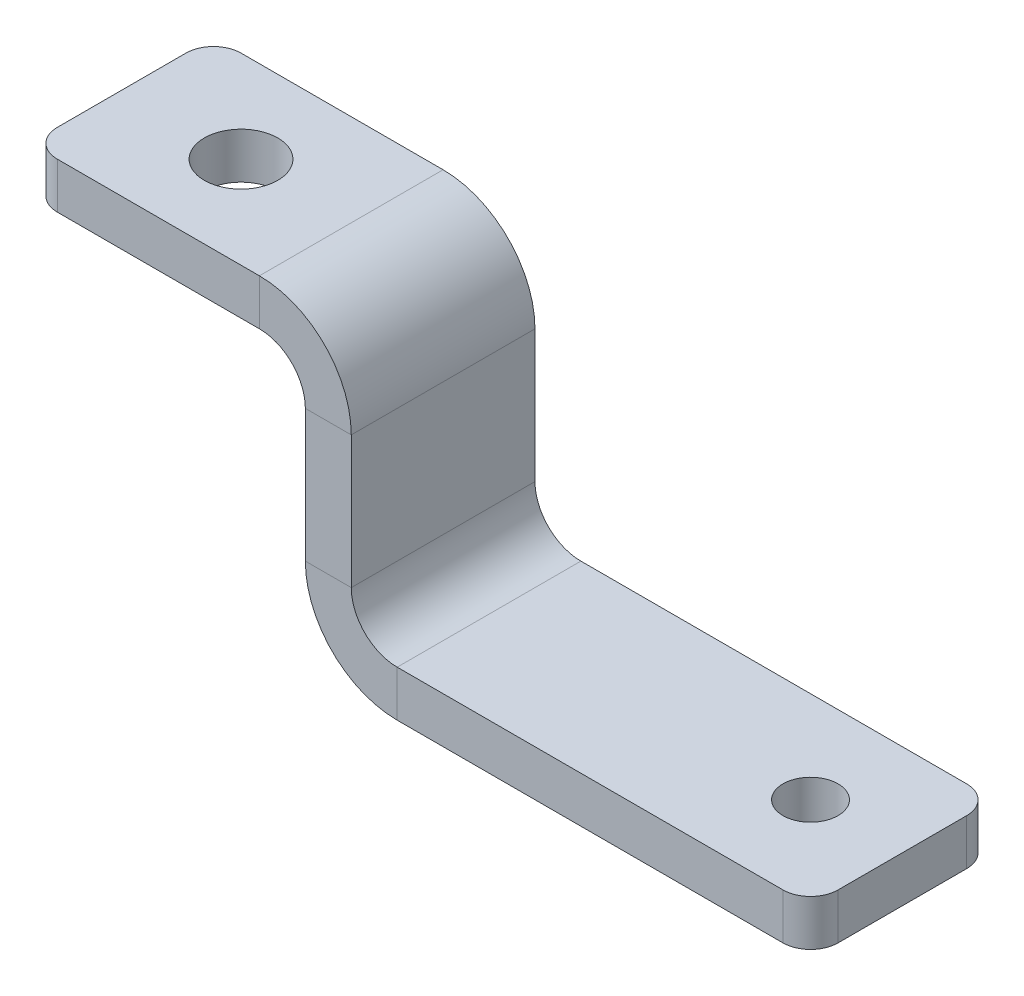
SolidWorks part; units mm, degrees
note: The reader was unsure of these and kept them because the rebuilt part matched: flange length of "Edge-Flange1", "Edge-Flange2".
ref_plane "Front Plane" through (0, 0, 0) normal (0, 0, 1) x (1, 0, 0)
ref_plane "Top Plane" through (0, 0, 0) normal (0, 1, 0) x (1, 0, 0)
ref_plane "Right Plane" through (0, 0, 0) normal (1, 0, 0) x (0, 0, -1)
sketch "Sketch1" plane through (0, 0, 0) normal (0, 1, 0) x (1, 0, 0)
  line L0 (-35, 10) -> (7, 10)
  line L1 (-35, -10) -> (7, -10)
  line L2 (10, 7) -> (10, -7)
  line L3 (-35, 10) -> (-35, -10)
  circle A0 centre (0, 0) radius 3
  arc A1 (7, 10) -> (10, 7) centre (7, 7) cw
  arc A2 (7, -10) -> (10, -7) centre (7, -7) ccw
  point P7 (10, 0)
  point P10 (10, 10)
  point P13 (10, -10)
  dimension "D1" = 6
  dimension "D6" = 3
  dimension "D2" = 20
  dimension "D3" = 45
  dimension "D4" = 45
  dimension "D5" = 10
base flange "Base-Flange1" sketch "Sketch1" thickness 5 reverse thickness direction no parameters "D1"=0.7366
edge flange "Edge-Flange1" sketch "Sketch11" flange angle 90 flange length 24.4 flange position bend outside bend radius 5 thickness 5 relief rectangular parameters "D6"=10
sketch "Sketch11" plane through (-35, 0, 0) normal (1, 0, 0) x (0, 0, -1)
  line L1 (10, 0) -> (-10, 0) construction
  line L2 (-10, 0) -> (-10, 19.4)
  line L3 (-10, 19.4) -> (10, 19.4)
  line L4 (10, 19.4) -> (10, 0)
  line L5 (10, 0) -> (-10, 0)
bend "EdgeBend1" bend radius 5 bend angle 90 parameters "D5"=1
edge flange "Edge-Flange2" sketch "Sketch14" flange angle 90 flange length 35 flange position bend outside bend radius 5 thickness 5 relief rectangular parameters "D6"=10
sketch "Sketch14" plane through (-45, 19.4, 0) normal (0, 1, 0) x (0, 0, -1)
  line L2 (-10, 0) -> (-10, 30)
  line L3 (-10, 30) -> (10, 30)
  line L4 (10, 30) -> (10, 0)
  line L5 (10, 0) -> (-10, 0) construction
  line L6 (10, 0) -> (-10, 0)
bend "EdgeBend2" bend radius 5 bend angle 90 parameters "D5"=2
sketch "Sketch15" plane through (0, 29.4, 0) normal (0, 1, 0) x (1, 0, 0)
  line L0 (-50, 10) -> (-50, -10) construction
  line L2 (-75, -10) -> (-50, -10) construction
  circle A0 centre (-62, 0) radius 4
  dimension "D1" = 8
  dimension "D2" = 12
  dimension "D3" = 10
extrude "Cut-Extrude1" cut sketch "Sketch15" against normal blind 5 normal cut yes
sketch "Sketch16" plane through (0, 29.4, 0) normal (0, 1, 0) x (1, 0, 0)
  line L0 (-75, -7) -> (-75, 7) construction
  line L1 (-72, 10) -> (-50, 10) construction
  line L2 (-72, -10) -> (-50, -10) construction
  line L3 (-75, 7) -> (-75, 10)
  line L4 (-75, 10) -> (-72, 10)
  line L5 (-75, -7) -> (-75, -10)
  line L6 (-75, -10) -> (-72, -10)
  arc A0 (-72, 10) -> (-75, 7) centre (-72, 7) ccw
  arc A1 (-75, -7) -> (-72, -10) centre (-72, -7) ccw
  point P10 (-75, 10)
  point P13 (-75, -10)
  dimension "D1" = 3
extrude "Cut-Extrude2" cut sketch "Sketch16" against normal blind 5 normal cut yes
sketch "Bend-Lines1" [suppressed] plane through (0, 0, 0) normal (0, 1, 0) x (1, 0, 0)
sketch "Bounding-Box1" [suppressed] plane through (0, 0, 0) normal (0, 1, 0) x (1, 0, 0)
sheet metal parameters "Sheet-Metal1" thickness 5 parameters "D1"=0.7366
flat pattern "Flat-Pattern1" [suppressed]
sketch "Bend-Lines2" plane through (0, 0, 0) normal (0, 1, 0) x (1, 0, 0)
sketch3d "Bounding-Box2" [suppressed]
  line L0 (18, -7, 0) -> (-7, -7, 0) construction
  line L1 (18, 13, 0) -> (-7, 13, 0) construction
  line L2 (18, -7, 0) -> (18, 13, 0) construction
  line L3 (-7, -7, 0) -> (-7, 13, 0) construction
sheet metal parameters "Sheet-Metal2" thickness 5 parameters "D1"=0.7366
flat pattern "Flat-Pattern1"
sketch "Bend-Lines2" plane through (0, 0, 0) normal (0, 1, 0) x (1, 0, 0)
  line L0 (-30.8905, 10) -> (-30.8905, -10) construction
  line L1 (-30.8905, 10) -> (-30.8905, -10) construction
sketch3d "Bounding-Box2" [suppressed]
  line L0 (-81.781, -7, 0) -> (7, -7, 0) construction
  line L1 (-81.781, 13, 0) -> (7, 13, 0) construction
  line L2 (-81.781, -7, 0) -> (-81.781, 13, 0) construction
  line L3 (7, -7, 0) -> (7, 13, 0) construction
bend of the flat pattern "Flatten-<EdgeBend1>1"
sheet metal parameters "Sheet-Metal3" thickness 5 parameters "D1"=0.7366
flat pattern "Flat-Pattern1"
sketch "Bend-Lines2" plane through (0, 0, 0) normal (0, 1, 0) x (1, 0, 0)
  line L0 (-30.8905, 10) -> (-30.8905, -10) construction
  line L1 (-30.8905, 10) -> (-30.8905, -10) construction
  line L2 (-54.0715, 10) -> (-54.0715, -10) construction
  line L3 (-54.0715, 10) -> (-54.0715, -10) construction
sketch3d "Bounding-Box2" [suppressed]
  line L0 (-92.9619, -7, 0) -> (7, -7, 0) construction
  line L1 (-92.9619, 13, 0) -> (7, 13, 0) construction
  line L2 (-92.9619, -7, 0) -> (-92.9619, 13, 0) construction
  line L3 (7, -7, 0) -> (7, 13, 0) construction
bend of the flat pattern "Flatten-<EdgeBend1>1"
bend of the flat pattern "Flatten-<EdgeBend2>1"
sheet metal parameters "Sheet-Metal4" thickness 5 parameters "D1"=0.7366
flat pattern "Flat-Pattern1"
sketch "Bend-Lines2" plane through (0, 0, 0) normal (0, 1, 0) x (1, 0, 0)
  line L0 (-30.8905, 10) -> (-30.8905, -10) construction
  line L1 (-30.8905, 10) -> (-30.8905, -10) construction
  line L2 (-54.0715, 10) -> (-54.0715, -10) construction
  line L3 (-54.0715, 10) -> (-54.0715, -10) construction
sketch3d "Bounding-Box2" [suppressed]
  line L0 (-92.9619, -7, 0) -> (7, -7, 0) construction
  line L1 (-92.9619, 13, 0) -> (7, 13, 0) construction
  line L2 (-92.9619, -7, 0) -> (-92.9619, 13, 0) construction
  line L3 (7, -7, 0) -> (7, 13, 0) construction
bend of the flat pattern "Flatten-<EdgeBend1>1"
bend of the flat pattern "Flatten-<EdgeBend2>1"
sheet metal parameters "Sheet-Metal5" thickness 5 parameters "D1"=0.7366
flat pattern "Flat-Pattern1"
sketch "Bend-Lines2" plane through (0, 0, 0) normal (0, 1, 0) x (1, 0, 0)
  line L0 (-40.8905, 10) -> (-40.8905, -10) construction
  line L1 (-40.8905, 10) -> (-40.8905, -10) construction
  line L2 (-67.0715, 10) -> (-67.0715, -10) construction
  line L3 (-67.0715, 10) -> (-67.0715, -10) construction
sketch3d "Bounding-Box2" [suppressed]
  line L0 (-104.9619, -3, 0) -> (3, -3, 0) construction
  line L1 (-104.9619, 17, 0) -> (3, 17, 0) construction
  line L2 (-104.9619, -3, 0) -> (-104.9619, 17, 0) construction
  line L3 (3, -3, 0) -> (3, 17, 0) construction
bend of the flat pattern "Flatten-<EdgeBend1>1"
bend of the flat pattern "Flatten-<EdgeBend2>1"
